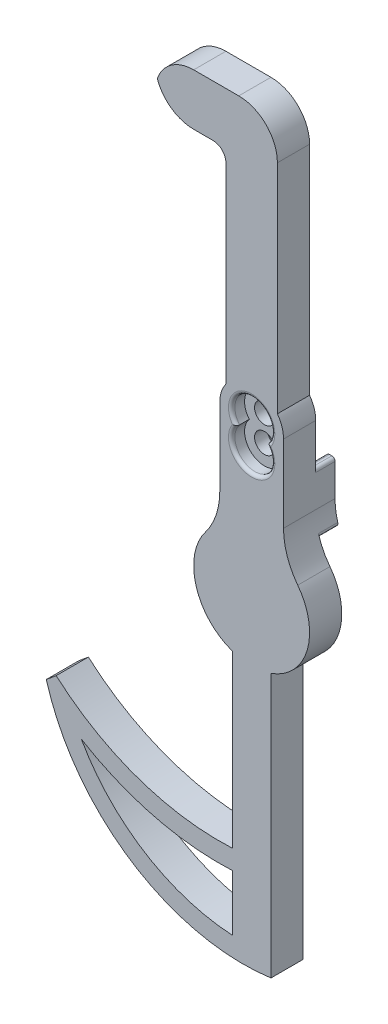
SolidWorks part; units mm, degrees
material "PLA"
ref_plane "Front Plane" through (0, 0, 0) normal (0, 0, 1) x (1, 0, 0)
ref_plane "Top Plane" through (0, 0, 0) normal (0, 1, 0) x (1, 0, 0)
ref_plane "Right Plane" through (0, 0, 0) normal (1, 0, 0) x (0, 0, -1)
sketch "Sketch1" plane through (0, 0, 0) normal (0, 0, 1) x (1, 0, 0)
  line L0 (-15.8075, -15.8075) -> (15.8075, 15.8075) construction
  line L1 (-15.8075, 15.8075) -> (15.8075, -15.8075) construction
  line L2 (0, 0) -> (0, 22.3552) construction
  line L3 (-3.5028, 12) -> (-3.35, 24)
  line L4 (-4.95, 12) -> (-4.95, 24)
  line L5 (4.95, 12) -> (4.95, 24)
  line L6 (3.5028, 12) -> (3.35, 24)
  line L9 (0.65, -3.8962) -> (0.65, -7.1706)
  line L10 (3.15, 12) -> (3.15, 24)
  line L11 (-3.15, 24) -> (-3.15, 12)
  line L12 (-0.65, -7.1706) -> (-0.65, -3.8962)
  line L13 (-0.65, 3.8962) -> (-0.65, 7.6481)
  line L14 (0.65, 7.6481) -> (0.65, 3.8962)
  line L15 (0.65, -3.8962) -> (0.65, -7.1706) construction
  line L16 (3.15, 12) -> (3.15, 24) construction
  line L17 (-3.15, 24) -> (-3.15, 12) construction
  line L18 (-0.65, -7.1706) -> (-0.65, -3.8962) construction
  line L19 (-0.65, 3.8962) -> (-0.65, 7.6481) construction
  line L20 (0.65, 7.6481) -> (0.65, 3.8962) construction
  circle A0 centre (0, 0) radius 22.3552 construction
  circle A1 centre (0, 20) radius 1.55
  circle A2 centre (0, 24) radius 1.55
  arc A3 (1.4948, 8.875) -> (-1.4948, 8.875) centre (0, 0) ccw
  circle A4 centre (-15.7528, 12) radius 12.25 construction
  arc A5 (-4.1855, 7.9675) -> (-3.5028, 12) centre (-15.7528, 12) ccw
  arc A6 (3.35, 24) -> (-3.35, 24) centre (0, 24) ccw
  circle A7 centre (-15.7528, 12) radius 10.8028 construction
  arc A9 (-4.95, 12) -> (-7.1593, 5.4538) centre (-15.7528, 12) cw
  arc A11 (-4.95, 24) -> (4.95, 24) centre (0, 24) cw
  arc A12 (0.65, -7.1706) -> (5.7275, 4.363) centre (0, 0) ccw
  arc A13 (3.15, 12) -> (5.7275, 4.363) centre (15.7528, 12) ccw
  arc A14 (3.15, 24) -> (-3.15, 24) centre (0, 24) ccw
  arc A15 (-5.7275, 4.363) -> (-3.15, 12) centre (-15.7528, 12) ccw
  arc A16 (-5.7275, 4.363) -> (-0.65, -7.1706) centre (0, 0) ccw
  arc A17 (-0.65, 3.8962) -> (-0.65, -3.8962) centre (0, 0) ccw
  arc A18 (0.65, 7.6481) -> (-0.65, 7.6481) centre (0, 9) ccw
  arc A19 (0.65, -3.8962) -> (0.65, 3.8962) centre (0, 0) ccw
  arc A20 (0.65, -7.1706) -> (5.7275, 4.363) centre (0, 0) ccw construction
  arc A21 (3.15, 12) -> (5.7275, 4.363) centre (15.7528, 12) ccw construction
  arc A22 (3.15, 24) -> (-3.15, 24) centre (0, 24) ccw construction
  arc A23 (-5.7275, 4.363) -> (-3.15, 12) centre (-15.7528, 12) ccw construction
  arc A24 (-5.7275, 4.363) -> (-0.65, -7.1706) centre (0, 0) ccw construction
  arc A25 (-0.65, 3.8962) -> (-0.65, -3.8962) centre (0, 0) ccw construction
  arc A26 (0.65, 7.6481) -> (-0.65, 7.6481) centre (0, 9) ccw construction
  arc A27 (0.65, -3.8962) -> (0.65, 3.8962) centre (0, 0) ccw construction
  arc A29 (-7.1593, 5.4538) -> (7.1593, 5.4538) centre (0, 0) ccw
  circle A30 centre (0, 0) radius 7.7902
  arc A31 (-4.1855, 7.9675) -> (-5.1734, 5.8243) centre (21.9382, -5.373) ccw
  arc A32 (4.1855, 7.9675) -> (5.1734, 5.8243) centre (-21.9382, -5.373) cw
  arc A33 (4.1855, 7.9675) -> (3.5028, 12) centre (15.7528, 12) cw
  arc A34 (4.95, 12) -> (7.1593, 5.4538) centre (15.7528, 12) ccw
  dimension "D1" = 3.1
  dimension "D2" = 3.1
  dimension "D6" = 18
  dimension "D8" = 24.5
  dimension "D9" = 15.5803
  dimension "D3" = 4
  dimension "D4" = 20
  dimension "D5" = 45
  dimension "D7" = 0
extrude "Boss-Extrude1" add sketch "Sketch1" along normal blind 4 contours A2 | A1 | A9 A29 A34 L5 A11 L4 region at (0, 20, 0) region at (0, 24, 0)
extrude "Boss-Extrude2" add sketch "Sketch1<6>" against normal blind 1 contours A9 A29 A34 L5 A11 L4 A33 A32 A30 A31 A5 L3 A6 L6 region at (-4.53, 18, 0)
sketch "Sketch1<6>" plane through (0, 0, 0) normal (0, 0, 1) x (1, 0, 0) same geometry as "Sketch1"
sketch "Sketch2" plane through (0, 0, -1) normal (0, 0, -1) x (-1, 0, 0)
  line L0 (3.583, 17.483) -> (3.6529, 11.9938)
  line L1 (0, 0) -> (0, 24) construction
  line L2 (4.95, 12) -> (4.95, 24)
  line L3 (-4.95, 24) -> (-4.95, 12)
  line L4 (4.95, 12) -> (4.95, 24)
  line L5 (-4.95, 24) -> (-4.95, 12)
  line L6 (3.5028, 12) -> (3.35, 24)
  line L7 (-3.35, 24) -> (-3.5028, 12)
  line L8 (3.5028, 12) -> (3.35, 24) construction
  line L9 (-3.35, 24) -> (-3.5028, 12) construction
  line L10 (4.95, 17.5004) -> (3.583, 17.483)
  line L11 (4.2882, 8.1307) -> (5.5172, 8.5455)
  line L12 (-3.583, 17.483) -> (-3.6529, 11.9938)
  line L13 (-4.95, 17.5004) -> (-3.583, 17.483)
  line L14 (-4.2882, 8.1307) -> (-5.5172, 8.5455)
  circle A0 centre (15.7528, 12) radius 12.0999 construction
  arc A1 (4.2882, 8.1307) -> (3.6529, 11.9938) centre (15.7528, 12) cw
  arc A2 (-4.2882, 8.1307) -> (-3.6529, 11.9938) centre (-15.7528, 12) ccw
  arc A4 (4.95, 12) -> (7.1593, 5.4538) centre (15.7528, 12) ccw
  arc A5 (4.95, 24) -> (-4.95, 24) centre (0, 24) ccw
  arc A6 (-7.1593, 5.4538) -> (-4.95, 12) centre (-15.7528, 12) ccw
  arc A7 (-7.1593, 5.4538) -> (7.1593, 5.4538) centre (0, 0) ccw
  arc A8 (4.95, 12) -> (7.1593, 5.4538) centre (15.7528, 12) ccw
  arc A9 (4.95, 24) -> (-4.95, 24) centre (0, 24) ccw
  arc A10 (-7.1593, 5.4538) -> (-4.95, 12) centre (-15.7528, 12) ccw
  arc A11 (-7.1593, 5.4538) -> (7.1593, 5.4538) centre (0, 0) ccw
  arc A14 (-4.1855, 7.9675) -> (-3.5028, 12) centre (-15.7528, 12) ccw
  arc A15 (-4.1855, 7.9675) -> (-5.1734, 5.8243) centre (21.9382, -5.373) ccw
  arc A16 (-5.1734, 5.8243) -> (5.1734, 5.8243) centre (0, 0) ccw
  arc A17 (5.1734, 5.8243) -> (4.1855, 7.9675) centre (-21.9382, -5.373) ccw
  arc A18 (3.5028, 12) -> (4.1855, 7.9675) centre (15.7528, 12) ccw
  arc A19 (3.35, 24) -> (-3.35, 24) centre (0, 24) ccw
  arc A20 (-4.1855, 7.9675) -> (-3.5028, 12) centre (-15.7528, 12) ccw construction
  arc A21 (-4.1855, 7.9675) -> (-5.1734, 5.8243) centre (21.9382, -5.373) ccw construction
  arc A22 (-5.1734, 5.8243) -> (5.1734, 5.8243) centre (0, 0) ccw construction
  arc A23 (5.1734, 5.8243) -> (4.1855, 7.9675) centre (-21.9382, -5.373) ccw construction
  arc A24 (3.5028, 12) -> (4.1855, 7.9675) centre (15.7528, 12) ccw construction
  arc A25 (3.35, 24) -> (-3.35, 24) centre (0, 24) ccw construction
  arc M20 (7.1593, 5.4538) -> (4.95, 12) centre (15.7528, 12) cw
  line M21 (4.95, 12) -> (4.95, 24)
  arc M24 (-4.95, 12) -> (-7.1593, 5.4538) centre (-15.7528, 12) cw
  dimension "D3" = 0.15
  dimension "D4" = 5.5
  dimension "D1" = 0
  dimension "D2" = 0
extrude "Boss-Extrude3" add sketch "Sketch2" along normal blind 3 contours A1 L11 L10 L0 M20 M21 | L14 A2 L12 L13 L5 M24 region at (-4.3663, 12.9319, -1) region at (4.3663, 12.9319, -1)
sketch "Sketch3" plane through (0, 0, 4) normal (0, 0, 1) x (1, 0, 0)
  circle A0 centre (0, 24) radius 1.55 construction
  circle A1 centre (0, 20) radius 1.55 construction
  circle A2 centre (0, 24) radius 1.55
  circle A3 centre (0, 20) radius 1.55
  circle A4 centre (0, 20) radius 3.1
  circle A5 centre (0, 24) radius 3.1
  dimension "D1" = 6.2
  dimension "D2" = 6.2
extrude "Cut-Extrude1" cut sketch "Sketch3" against normal blind 2
fillet "Fillet2" radius 0.5 10 edges at (-3.583, 17.483, -2.5) (-4.95, 17.5004, -2.5) (3.583, 17.483, -2.5) (-5.5172, 8.5455, -2.5) (-4.2882, 8.1307, -2.5) (4.95, 17.5004, -2.5) (5.5172, 8.5455, -2.5) (4.2882, 8.1307, -2.5) (0, 27.1, 4) (0, 16.9, 4)
ref_plane "Plane1" through (0, 0, 5) normal (0, 0, 1) x (1, 0, 0)
sketch "Sketch4" plane through (0, 0, 4) normal (0, 0, 1) x (1, 0, 0)
  line L0 (0, 0) -> (34.7263, 0) construction
  line L1 (0, 0) -> (25.4725, -30.357) construction
  line L2 (25.4725, -30.357) -> (26.7581, -31.8891)
  line L3 (34.7263, 0) -> (49.7263, 0)
  line L4 (35, -3) -> (8.4853, -3)
  line L5 (35, 3) -> (8.4853, 3)
  line L6 (35, 3) -> (49.7263, 3)
  line L7 (49.7263, 3) -> (49.7263, 0)
  line L9 (38.0037, -3) -> (46.7056, -3)
  circle A0 centre (0, 0) radius 9
  arc A3 (34.7263, 0) -> (25.4725, -30.357) centre (-3.3379, -4.9858) cw
  arc A4 (49.7263, 0) -> (26.7581, -31.8891) centre (17.9508, -1.3297) cw
  circle A5 centre (17.9508, -1.3297) radius 31.8032 construction
  arc A6 (49.7263, 0) -> (49.458, 3) centre (17.9508, -1.3297) ccw
  circle A7 centre (17.9508, -1.3297) radius 28.8032 construction
  circle A8 centre (-3.3379, -4.9858) radius 41.3893 construction
  arc A9 (38.0037, -3) -> (32.0548, -26.4435) centre (-3.3379, -4.9858) cw
  arc A10 (46.7056, -3) -> (32.0548, -26.4435) centre (17.9508, -1.3297) cw
  point P20 (32.0548, -26.4435)
  arc M20 (-7.1593, 5.4538) -> (7.1593, 5.4538) centre (0, 0) ccw
  dimension "D1" = 18
  dimension "D2" = 35
  dimension "D4" = 6
  dimension "D8" = 18
  dimension "D9" = 3
  dimension "D10" = 3
  dimension "D3" = 2
  dimension "D5" = 15
  dimension "D6" = 50
  dimension "D7" = 3
extrude "Boss-Extrude4" add sketch "Sketch4" against normal up to surface (5 mm away) contours A3 L3 L7 L6 L5 L4 M20 | L3 A3 L2 L9 region at (33.2943, -17.7435, 4) region at (26.3516, 0.3286, 4) up to face at (0, 12.7161, -1)
sketch "Sketch5" plane through (0, 0, 4) normal (0, 0, 1) x (1, 0, 0)
  line L0 (0, 0) -> (0, 62.6797) construction
  line L1 (0, 0) -> (-32.3114, 53.7096) construction
  line L8 (0, 62.6797) -> (-15, 62.6797) construction
  line L9 (-15, 58.6797) -> (-15, 66.6797)
  line L10 (-15, 66.6797) -> (4, 66.6797)
  line L11 (4, 66.6797) -> (4, 26.9159)
  line L12 (-15, 58.6797) -> (4, 58.6797)
  line L13 (-4, 66.6797) -> (-4, 26.9159)
  arc A2 (4.95, 24) -> (-4.95, 24) centre (0, 24) ccw construction
  arc A3 (-4, 26.9159) -> (4, 26.9159) centre (0, 22.3879) cw
  arc M19 (4.95, 24) -> (-4.95, 24) centre (0, 24) ccw
  dimension "D1" = 62.6797
  dimension "D2" = 15
  dimension "D3" = 4
  dimension "D4" = 4
extrude "Boss-Extrude5" add sketch "Sketch5" against normal up to surface (5 mm away) contours L12 L13 L11 M19 | L10 L13 L12 L11 | L13 L10 L9 L12 region at (-9.5, 62.6797, 4) region at (0, 62.6797, 4) region at (0, 43.5042, 4) up to face at (5.6426, 7.7752, -1)
fillet "Fillet3" radius 2 1 edges at (-4, 58.6797, 1.5)
pattern_circular "CirPattern1" count 2 over 90 about axis through (0, 0, 4) along (0, 0, 1) of "Boss-Extrude4" reverse direction yes
sketch "Sketch6" plane through (0, 0, 4) normal (0, 0, 1) x (1, 0, 0)
  line L1 (7.8026, 12.6303) -> (57.0764, 12.6303)
  line L2 (7.8026, 12.6303) -> (7.8026, -35)
  line L3 (7.8026, -35) -> (57.0764, -35)
  line L4 (57.0764, 12.6303) -> (57.0764, -35)
  line L12 (-15, 58.6797) -> (-6, 58.6797)
  line L13 (-4, 56.6797) -> (-4, 26.9159)
  line L14 (-4.95, 24) -> (-4.95, 12)
  line L15 (-3, -8.4853) -> (-3, -35)
  line L16 (-30.357, -25.4725) -> (-31.8891, -26.7581)
  line L17 (3, -49.458) -> (3, -8.4853)
  line L18 (8.4853, -3) -> (35, -3)
  line L19 (25.4725, -30.357) -> (26.7581, -31.8891)
  line L20 (49.458, 3) -> (8.4853, 3)
  line L21 (4.95, 12) -> (4.95, 24)
  line L22 (4, 26.9159) -> (4, 66.6797)
  line L23 (4, 66.6797) -> (-15, 66.6797)
  line L24 (-15, 58.6797) -> (-6, 58.6797)
  line L25 (-4, 56.6797) -> (-4, 26.9159)
  line L26 (-4.95, 24) -> (-4.95, 12)
  line L27 (-3, -8.4853) -> (-3, -35)
  line L28 (-30.357, -25.4725) -> (-31.8891, -26.7581)
  line L29 (3, -49.458) -> (3, -8.4853)
  line L30 (8.4853, -3) -> (35, -3)
  line L31 (25.4725, -30.357) -> (26.7581, -31.8891)
  line L32 (49.458, 3) -> (8.4853, 3)
  line L33 (4.95, 12) -> (4.95, 24)
  line L34 (4, 26.9159) -> (4, 66.6797)
  line L35 (4, 66.6797) -> (-15, 66.6797)
  line L41 (-15, 66.6797) -> (-15, 58.6797)
  line L42 (-15, 66.6797) -> (-15, 58.6797)
  circle A0 centre (0, 0) radius 9
  arc A17 (-4, 56.6797) -> (-6, 58.6797) centre (-6, 56.6797) ccw
  arc A18 (-4, 26.9159) -> (-4.95, 24) centre (0, 24) ccw
  arc A19 (-7.1593, 5.4538) -> (-4.95, 12) centre (-15.7528, 12) ccw
  arc A20 (-7.1593, 5.4538) -> (-3, -8.4853) centre (0, 0) ccw
  arc A21 (-30.357, -25.4725) -> (-3, -35) centre (-4.9858, 3.3379) ccw
  arc A22 (-31.8891, -26.7581) -> (3, -49.458) centre (-1.3297, -17.9508) ccw
  arc A23 (3, -8.4853) -> (8.4853, -3) centre (0, 0) ccw
  arc A24 (25.4725, -30.357) -> (35, -3) centre (-3.3379, -4.9858) ccw
  arc A25 (26.7581, -31.8891) -> (49.458, 3) centre (17.9508, -1.3297) ccw
  arc A26 (8.4853, 3) -> (7.1593, 5.4538) centre (0, 0) ccw
  arc A27 (4.95, 12) -> (7.1593, 5.4538) centre (15.7528, 12) ccw
  arc A28 (4.95, 24) -> (4, 26.9159) centre (0, 24) ccw
  arc A32 (-4, 56.6797) -> (-6, 58.6797) centre (-6, 56.6797) ccw
  arc A33 (-4, 26.9159) -> (-4.95, 24) centre (0, 24) ccw
  arc A34 (-7.1593, 5.4538) -> (-4.95, 12) centre (-15.7528, 12) ccw
  arc A35 (-7.1593, 5.4538) -> (-3, -8.4853) centre (0, 0) ccw
  arc A36 (-30.357, -25.4725) -> (-3, -35) centre (-4.9858, 3.3379) ccw
  arc A37 (-31.8891, -26.7581) -> (3, -49.458) centre (-1.3297, -17.9508) ccw
  arc A38 (3, -8.4853) -> (8.4853, -3) centre (0, 0) ccw
  arc A39 (25.4725, -30.357) -> (35, -3) centre (-3.3379, -4.9858) ccw
  arc A40 (26.7581, -31.8891) -> (49.458, 3) centre (17.9508, -1.3297) ccw
  arc A41 (8.4853, 3) -> (7.1593, 5.4538) centre (0, 0) ccw
  arc A42 (4.95, 12) -> (7.1593, 5.4538) centre (15.7528, 12) ccw
  arc A43 (4.95, 24) -> (4, 26.9159) centre (0, 24) ccw
  arc M45 (3, -8.4853) -> (8.4853, -3) centre (0, 0) ccw
  line M46 (8.4853, -3) -> (35, -3)
  arc M47 (35, -3) -> (25.4725, -30.357) centre (-3.3379, -4.9858) cw
  line M48 (25.4725, -30.357) -> (26.7581, -31.8891)
  arc M49 (26.7581, -31.8891) -> (49.458, 3) centre (17.9508, -1.3297) ccw
  line M50 (49.458, 3) -> (8.4853, 3)
  arc M51 (8.4853, 3) -> (7.1593, 5.4538) centre (0, 0) ccw
  line M58 (38.0037, -3) -> (46.7056, -3)
  arc M59 (46.7056, -3) -> (32.0548, -26.4435) centre (17.9508, -1.3297) cw
  arc M60 (32.0548, -26.4435) -> (38.0037, -3) centre (-3.3379, -4.9858) ccw
  dimension "D1" = 0
extrude "Cut-Extrude2" cut sketch "Sketch6" against normal blind 10 contours L4 L1 L2 L3 M51 M50 M49 M48 M47 M46 M45 | A0 M46 M47 M48 M49 M50 M60 M58 M59 | M58 M60 M59 region at (31.7832, -11.9956, 4) region at (28.9716, 2.4596, 4) region at (40.3855, -12.1692, 4)
fillet "Fillet4" radius 6 3 edges at (4, 66.6797, 1.5) (-15, 66.6797, 1.5) (-15, 58.6797, 1.5)
equation "\"O_R\"= 4'Outer radius (Addendum)"
equation "\"I_R\"= 2.9'Inner radius (Dedendum)"
equation "\"N\"= 25'# of teeth"
equation "\"phi\"= 20'Pressure angle"
equation "\"P_R\"= 3'Pitch radius"
equation "\"a\"= ( \"period\" - ( \"err\" + \"T_F\" ) * ( \"I_R\" ) ) / ( 1 + ( \"O_R\" / \"I_R\" ) )'Outer arc degree"
equation "\"a_i\"= \"a\" * \"O_R\" / \"I_R\"'Inner arc degree (+manufacturing)"
equation "\"err\"= .03'Manufacturing error"
equation "\"period\"= 360 / \"N\"'Period of gear teeth"
equation "\"T_F\"= \"O_R\" / 2cm'Transition factor for curve"
equation "\"D4@Sketch19\"= \"a_i\" / 2"
